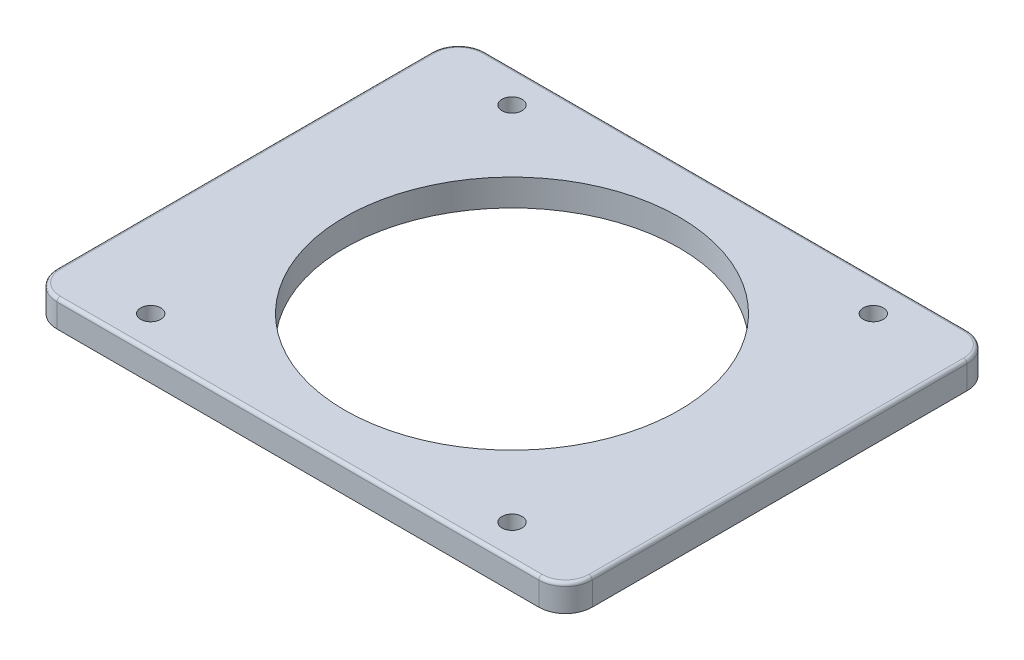
SolidWorks part; units mm, degrees
ref_plane "Front Plane" through (0, 0, 0) normal (0, 0, 1) x (1, 0, 0)
ref_plane "Top Plane" through (0, 0, 0) normal (0, 1, 0) x (1, 0, 0)
ref_plane "Right Plane" through (0, 0, 0) normal (1, 0, 0) x (0, 0, -1)
sketch "Sketch1" plane through (0, 0, 0) normal (0, 1, 0) x (1, 0, 0)
  line L1 (-20, -16) -> (20, -16)
  line L2 (-20, -16) -> (-20, 16)
  line L3 (-20, 16) -> (20, 16)
  line L4 (20, -16) -> (20, 16)
  line L5 (-20, -16) -> (20, 16) construction
  line L6 (-20, 16) -> (20, -16) construction
  line L7 (-13.5, -13.5) -> (13.5, -13.5) construction
  line L8 (-13.5, -13.5) -> (-13.5, 13.5) construction
  line L9 (-13.5, 13.5) -> (13.5, 13.5) construction
  line L10 (13.5, -13.5) -> (13.5, 13.5) construction
  line L11 (-13.5, -13.5) -> (13.5, 13.5) construction
  line L12 (-13.5, 13.5) -> (13.5, -13.5) construction
  circle A0 centre (0, 0) radius 12.5
  circle A1 centre (-13.5, 13.5) radius 0.75
  circle A2 centre (13.5, 13.5) radius 0.75
  circle A3 centre (13.5, -13.5) radius 0.75
  circle A4 centre (-13.5, -13.5) radius 0.75
  point P0 (0, 0)
  point P22 (0, 0)
  dimension "D3" = 25
  dimension "D4" = 1.5
  dimension "D1" = 40
  dimension "D2" = 32
  dimension "D5" = 27
  dimension "D6" = 27
  dimension "D7" = 4
extrude "Boss-Extrude1" add sketch "Sketch1" along normal blind 2
fillet "Fillet1" radius 0.25 4 edges at (20, 2, 0) (0, 2, -16) (-20, 2, 0) (0, 2, 16)
fillet "Fillet2" radius 2 8 edges at (19.9268, 1.9268, 15.9268) (19.9268, 1.9268, -15.9268) (-19.9268, 1.9268, 15.9268) (-19.9268, 1.9268, -15.9268) (-20, 0.875, -16) (-20, 0.875, 16) (20, 0.875, -16) (20, 0.875, 16)
